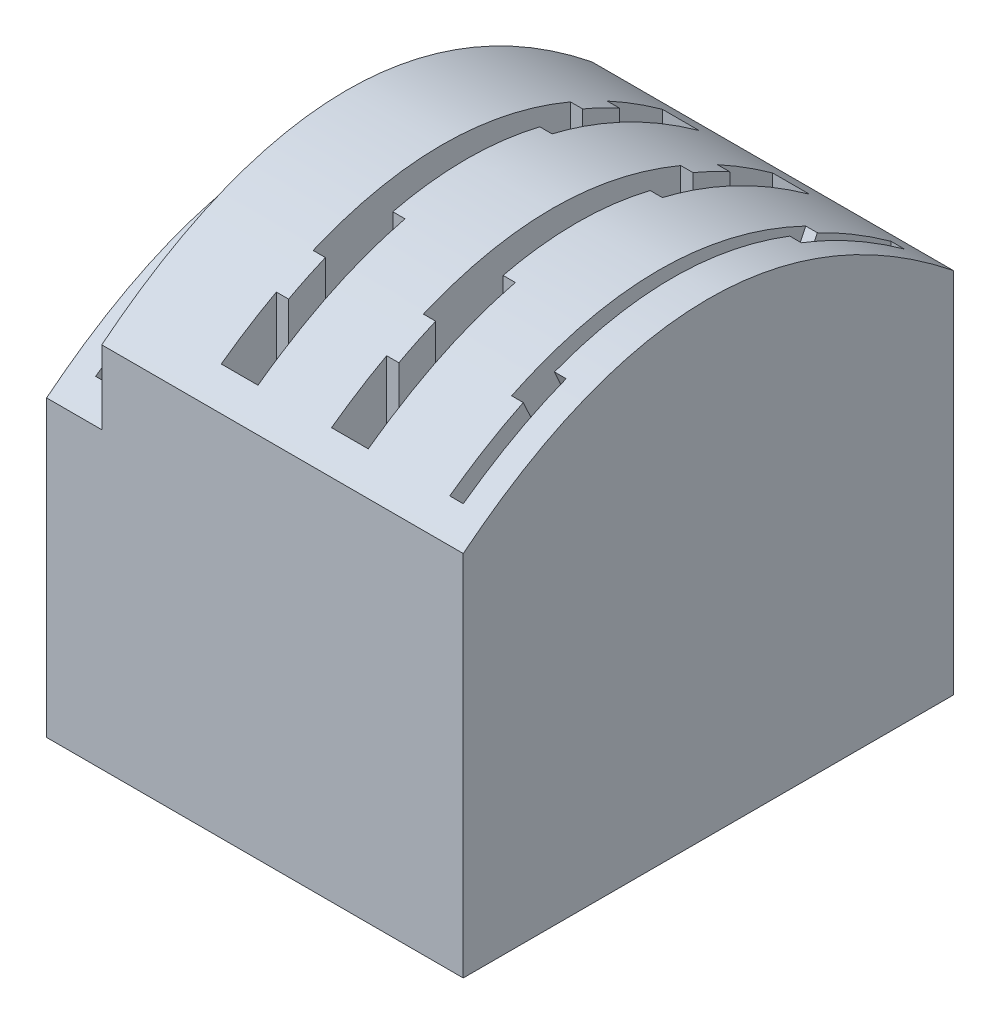
SolidWorks part; units mm, degrees
ref_plane "Front Plane" through (0, 0, 0) normal (0, 0, 1) x (1, 0, 0)
ref_plane "Top Plane" through (0, 0, 0) normal (0, 1, 0) x (1, 0, 0)
ref_plane "Right Plane" through (0, 0, 0) normal (1, 0, 0) x (0, 0, -1)
sketch "Sketch1" plane through (0, 0, 0) normal (1, 0, 0) x (0, 0, -1)
  line L2 (-100, 85) -> (-100, -65)
  line L3 (-100, -65) -> (100, -65)
  line L4 (100, 85) -> (100, -65)
  spline S0 degree 2 poles (-100, 85) (0, 165) (100, 85) knots 0 0 0 1 1 1
  point P4 (-100, 85)
  point P5 (100, 85)
  dimension "D1" = 200
  dimension "D2" = 100
  dimension "D3" = 150
  dimension "D4" = 150
  dimension "D5" = 40
  dimension "D6" = 100
  dimension "D7" = 125
extrude "Base" add sketch "Sketch1" along normal blind 170
ref_plane "New Top" through (0, 125, 0) normal (0, 1, 0) x (1, 0, 0)
sketch "Sketch3" plane through (0, 125, 0) normal (0, 1, 0) x (1, 0, 0)
  line L0 (170, -100) -> (170, 100) construction
  line L1 (121.25, 90) -> (106.25, 90)
  line L2 (121.25, 90) -> (121.25, 30)
  line L3 (121.25, -90) -> (106.25, -90)
  line L4 (106.25, 90) -> (106.25, 67.5)
  line L5 (91.25, -104.5688) -> (91.25, 145.9081) construction
  line L6 (106.25, 52.5) -> (111.25, 52.5)
  line L7 (170, 100) -> (0, 100) construction
  line L12 (170, -100) -> (0, -100) construction
  line L14 (106.25, 67.5) -> (111.25, 67.5)
  line L15 (111.25, 52.5) -> (111.25, 67.5)
  line L16 (121.25, 30) -> (116.25, 30)
  line L18 (121.25, -30) -> (116.25, -30)
  line L19 (116.25, 30) -> (116.25, -30)
  line L20 (106.25, -67.5) -> (111.25, -67.5)
  line L22 (106.25, -52.5) -> (111.25, -52.5)
  line L23 (111.25, -67.5) -> (111.25, -52.5)
  line L24 (76.25, 90) -> (61.25, 90)
  line L25 (76.25, 90) -> (76.25, 30)
  line L26 (76.25, -90) -> (61.25, -90)
  line L27 (61.25, 90) -> (61.25, 67.5)
  line L28 (61.25, 52.5) -> (66.25, 52.5)
  line L30 (61.25, 67.5) -> (66.25, 67.5)
  line L31 (66.25, 52.5) -> (66.25, 67.5)
  line L32 (76.25, 30) -> (71.25, 30)
  line L34 (76.25, -30) -> (71.25, -30)
  line L35 (71.25, 30) -> (71.25, -30)
  line L36 (61.25, -67.5) -> (66.25, -67.5)
  line L38 (61.25, -52.5) -> (66.25, -52.5)
  line L39 (66.25, -67.5) -> (66.25, -52.5)
  line L40 (121.25, -30) -> (121.25, -90)
  line L41 (76.25, -30) -> (76.25, -90)
  line L42 (61.25, 52.5) -> (61.25, -52.5)
  line L45 (61.25, -67.5) -> (61.25, -90)
  line L46 (106.25, -67.5) -> (106.25, -90)
  line L47 (106.25, 52.5) -> (106.25, -52.5)
  dimension "D1" = 48.75
  dimension "D2" = 15
  dimension "D3" = 15
  dimension "D4" = 2
  dimension "D5" = 15
  dimension "10" = 10
  dimension "D8" = 10
  dimension "D9" = 22.5
  dimension "D10" = 15
  dimension "D11" = 5
  dimension "D12" = 5
  dimension "D13" = 22.5
  dimension "D14" = 22.5
  dimension "D15" = 22.5
  dimension "D16" = 15
  dimension "D17" = 5
sketch "Sketch4" plane through (0, 125, 0) normal (0, 1, 0) x (1, 0, 0)
  line L1 (22.5, 87.5) -> (10, 87.5)
  line L2 (22.5, 87.5) -> (22.5, -87.5)
  line L3 (22.5, -87.5) -> (10, -87.5)
  line L4 (10, 87.5) -> (10, -87.5)
  line L5 (170, 100) -> (0, 100) construction
  line L6 (170, -100) -> (0, -100) construction
  line L7 (0, 100) -> (0, -100) construction
  dimension "D1" = 10
  dimension "D2" = 12.5
  dimension "D3" = 12.5
  dimension "D4" = 12.5
sketch "Sketch5" plane through (0, 125, 0) normal (0, 1, 0) x (1, 0, 0)
  line L0 (170, -100) -> (170, 100) construction
  line L1 (160, 90) -> (154.5, 90)
  line L2 (160, 90) -> (160, 48)
  line L3 (160, -90) -> (154.5, -90)
  line L4 (149.75, 60) -> (149.75, -60)
  line L5 (170, 100) -> (0, 100) construction
  line L6 (170, -100) -> (0, -100) construction
  line L7 (160, -48) -> (160, -90)
  line L10 (149.75, 60) -> (154.5, 60)
  line L11 (154.5, 90) -> (154.5, 60)
  line L12 (160, 48) -> (155.25, 48)
  line L14 (160, -48) -> (155.25, -48)
  line L15 (155.25, 48) -> (155.25, -48)
  line L18 (149.75, -60) -> (154.5, -60)
  line L19 (154.5, -90) -> (154.5, -60)
  dimension "D1" = 5.5
  dimension "D3" = 10
  dimension "D4" = 10
  dimension "D5" = 10
  dimension "D6" = 30
  dimension "D7" = 30
  dimension "D8" = 5.5
  dimension "D9" = 12
  dimension "D10" = 12
  dimension "D11" = 5.5
extrude "Flaps Cut" cut sketch "Sketch5" against normal up to surface (190 mm away) up to face at (85, -65, 0)
extrude "Throttle Cut" cut sketch "Sketch3" against normal up to surface (190 mm away) up to face at (155.6667, -65, 0)
extrude "Wing Sweep Cut" cut sketch "Sketch4" against normal up to surface (190 mm away) up to face at (112.5, -65, 0)
sketch "Sketch7" plane through (0, -65, 0) normal (0, -1, 0) x (1, 0, 0)
  line L0 (170, 100) -> (0, 100) construction
  line L1 (10, 90) -> (160, 90)
  line L2 (10, 90) -> (10, -90)
  line L3 (10, -90) -> (160, -90)
  line L4 (160, 90) -> (160, -90)
  dimension "D1" = 10
extrude "Bottom Cut" cut sketch "Sketch7" against normal blind 140
sketch "Sketch20" plane through (155.25, 0, 0) normal (-1, 0, 0) x (0, 0, 1)
  line L0 (48, 115.784) -> (25.5, 65.784)
  line L1 (25.5, 65.784) -> (48, 65.784)
  line L2 (48, 65.784) -> (48, 115.784)
  line L3 (-48, 115.784) -> (-48, 65.784)
  line L4 (-48, 65.784) -> (-24.5, 65.784)
  line L5 (-24.5, 65.784) -> (-48, 115.784)
  dimension "D1" = 90
  dimension "D2" = 22.5
  dimension "D3" = 50
  dimension "D4" = 50
  dimension "D5" = 23.5
extrude "Cut-Extrude10" cut sketch "Sketch20" against normal blind 4.75
sketch "Sketch22" plane through (160, 0, 0) normal (-1, 0, 0) x (0, 0, 1)
  line L0 (-60, 110.6) -> (-43, 75)
  line L2 (-43, 75) -> (-60, 75)
  line L3 (-60, 75) -> (-60, 110.6)
  line L4 (-60, 75) -> (-60, 110.6) construction
  line L5 (60, 110.6) -> (60, 75)
  line L11 (60, 75) -> (43.75, 75)
  line L12 (43.75, 75) -> (60, 110.6)
  line L13 (-90, 75) -> (-60, 75) construction
  line L14 (60, 75) -> (90, 75) construction
  dimension "D1" = 0
  dimension "D2" = 17
  dimension "D3" = 90
  dimension "D4" = 0
  dimension "D5" = 16.25
  dimension "D6" = 0
  dimension "D7" = 0
  dimension "D8" = 0
extrude "Boss-Extrude5" add sketch "Sketch22" against normal blind 4.75 from surface starting at face at (149.75, 92.8, 15)
sketch "Sketch9" plane through (0, 0, 0) normal (-1, 0, 0) x (0, 0, 1)
  line L0 (100, 85) -> (100, -65) construction
  line L1 (-100, 55) -> (-100, 135)
  line L2 (-100, 135) -> (100, 135)
  line L3 (100, 135) -> (100, 55)
  spline S0 degree 2 poles (-100, 55) (0, 135) (100, 55) knots 0 0 0 1 1 1
  dimension "D1" = 100
  dimension "D2" = 40
  dimension "D3" = 100
  dimension "D4" = 40
  dimension "D5" = 0
  dimension "D6" = 30
  dimension "D7" = 80
extrude "Cut-Extrude4" cut sketch "Sketch9" against normal up to surface (22.5 mm away) up to face at (22.5, 84.6875, -21.875)
sketch "Sketch13" plane through (0, 75, 0) normal (0, -1, 0) x (1, 0, 0)
  line L0 (61.25, 90) -> (22.5, 90) construction
  line L1 (22.5, 90) -> (32.5, 90)
  line L2 (22.5, 90) -> (22.5, -90)
  line L3 (22.5, -90) -> (32.5, -90)
  line L4 (32.5, 90) -> (32.5, -90)
  line L5 (22.5, -90) -> (61.25, -90) construction
  dimension "D1" = 10
  dimension "D2" = 0
  dimension "D3" = 0
extrude "Boss-Extrude2" add sketch "Sketch13" along normal blind 140
sketch "Sketch12" plane through (22.5, 0, 0) normal (-1, 0, 0) x (0, 0, 1)
  line L0 (-48.4309, 58.2758) -> (-48.4309, 55.2758)
  line L1 (100, 27.75) -> (100, 24.75)
  spline S0 degree 3 poles (-48.4309, 58.2758) (3.558, 77.5898) (53.0349, 67.4145) (100, 27.75) knots 0.031016 0.031016 0.031016 0.031016 1 1 1 1
  spline S1 degree 3 poles (100, 24.75) (53.0349, 64.4145) (3.558, 74.5898) (-48.4309, 55.2758) knots 0 0 0 0 0.968984 0.968984 0.968984 0.968984
  point P0 (0, 64.75)
  point P2 (100, 24.75)
  point P4 (0, 67.75)
  point P5 (-100, 23.75)
  point P6 (100, 27.75)
  dimension "D1" = 100
  dimension "D4" = 40
  dimension "D5" = 40
  dimension "D6" = 100
  dimension "D8" = 27.25
  dimension "D9" = 3
extrude "Boss-Extrude1" add sketch "Sketch12" along normal blind 2.5
sketch "Sketch17" plane through (22.5, 0, 0) normal (-1, 0, 0) x (0, 0, 1)
  line L0 (-49.7797, 57.8455) -> (-56.5642, 70.771)
  line L1 (-56.5642, 70.771) -> (-59.2205, 69.3767)
  line L2 (-59.2205, 69.3767) -> (-51.0872, 53.8816)
  line L3 (-51.0872, 53.8816) -> (-48.4309, 55.2758)
  line L5 (-48.4309, 58.2758) -> (-49.7797, 57.8455)
  line L6 (-48.4309, 58.2758) -> (-48.4309, 55.2758)
  dimension "D1" = 90
  dimension "25" = 17.5
  dimension "D2" = 3
  dimension "D3" = 90
  dimension "D4" = 90
  dimension "D5" = 100
extrude "Boss-Extrude3" add sketch "Sketch17" along normal blind 2.5
sketch "Sketch19" plane through (22.5, 0, 0) normal (-1, 0, 0) x (0, 0, 1)
  line L0 (-100, -65) -> (-100, 55) construction
  line L1 (-55.7563, 69.232) -> (-56.9133, 71.6936)
  line L2 (-49.7797, 57.8455) -> (-56.5642, 70.771) construction
  line L3 (-100, 45.5) -> (-100, 42.5)
  spline S0 degree 2 poles (-100, 42.5) (-76.9596, 59.4626) (-55.7563, 69.232) knots 0 0 0 0.212033 0.212033 0.212033
  spline S1 degree 2 poles (-100, 45.5) (-77.5381, 61.9998) (-56.9133, 71.6936) knots 0 0 0 0.206248 0.206248 0.206248
  dimension "D6" = 12.5
  dimension "D4" = 26.732
  dimension "D3" = 2.7199
  dimension "D5" = 0
  dimension "D11" = 0
  dimension "D12" = 3
extrude "Boss-Extrude4" add sketch "Sketch19" along normal blind 2.5
fillet "Fillet1" radius 2.5 4 edges at (21.25, 53.8816, -51.0872) (21.25, 57.8455, -49.7797) (21.25, 67.954, -58.4737) (21.25, 71.6936, -56.9133)
sketch "Sketch23" plane through (170, 0, 0) normal (1, 0, 0) x (0, 0, -1)
  circle A0 centre (0, 0) radius 9.5
  circle A1 centre (0, 0) radius 6
  dimension "D1" = 19
  dimension "D2" = 12
extrude "Boss-Extrude6" add sketch "Sketch23" against normal blind 5 from surface starting at face at (160, 54.596, -5.148)
sketch "Sketch24" plane through (32.5, 0, 0) normal (1, 0, 0) x (0, 0, -1)
  line L1 (90, -65) -> (-90, -65) construction
  circle A0 centre (0, -27.5) radius 7.5
  dimension "D1" = 15
  dimension "D2" = 0
  dimension "D3" = 37.5
extrude "Cut-Extrude11" cut sketch "Sketch24" against normal blind 10
